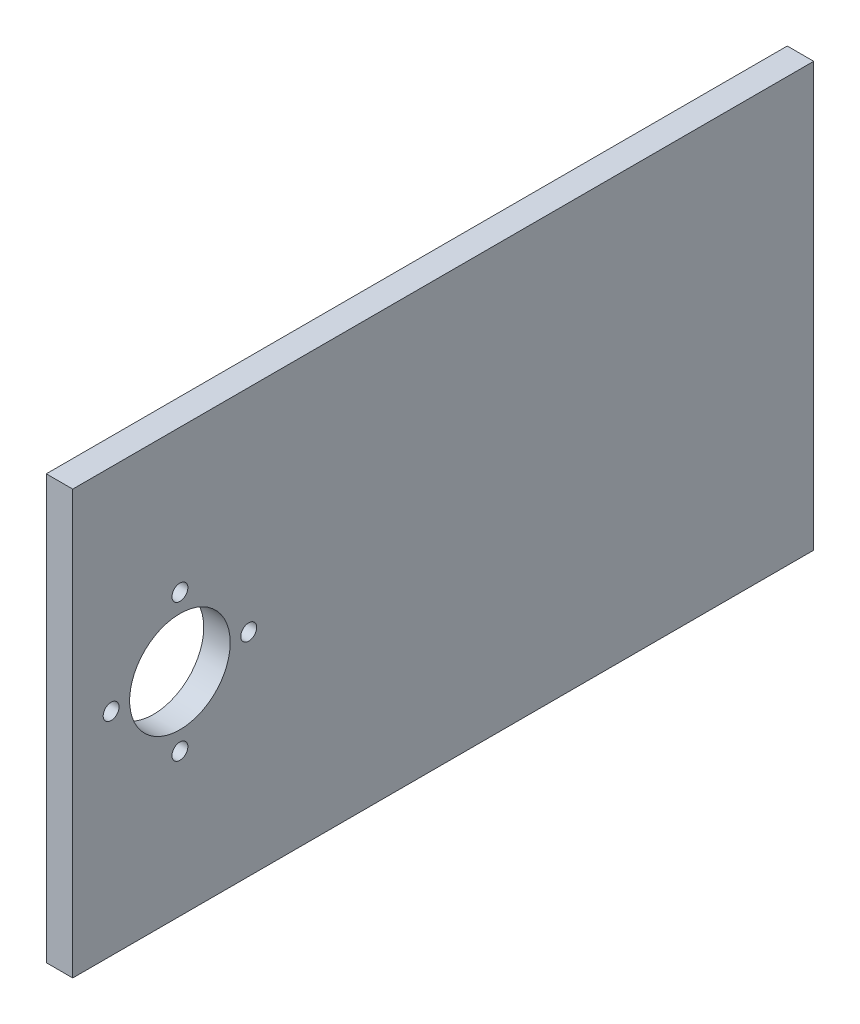
SolidWorks part; units mm, degrees
ref_plane "Front Plane" through (0, 0, 0) normal (1, 0, 0) x (0, 1, 0)
ref_plane "Top Plane" through (0, 0, 0) normal (0, 0, 1) x (0, 1, 0)
ref_plane "Right Plane" through (0, 0, 0) normal (0, 1, 0) x (-1, 0, 0)
sketch "Sketch1" plane through (0, 0, 0) normal (1, 0, 0) x (0, 1, 0)
  line L0 (0, 70) -> (0, -70) construction
  line L1 (-40, -70) -> (40, -70)
  line L2 (-40, -70) -> (-40, 70)
  line L3 (-40, 70) -> (40, 70)
  line L4 (40, -70) -> (40, 70)
  line L5 (-40, -70) -> (40, 70) construction
  line L6 (-40, 70) -> (40, -70) construction
  line L7 (-40, 49.75) -> (40, 49.75) construction
  circle A1 centre (0, 62.75) radius 1.5
  circle A2 centre (0, 36.75) radius 1.5
  circle A3 centre (-13, 49.75) radius 1.5
  circle A4 centre (13, 49.75) radius 1.5
  circle A5 centre (0, 49.75) radius 9.5
  point P0 (0, 0)
  dimension "D5" = 3
  dimension "D6" = 3
  dimension "D7" = 13
  dimension "D8" = 19
  dimension "D1" = 80
  dimension "D2" = 140
  dimension "D3" = 119.75
  dimension "D4" = 13
extrude "Boss-Extrude1" add sketch "Sketch1" along normal blind 5
